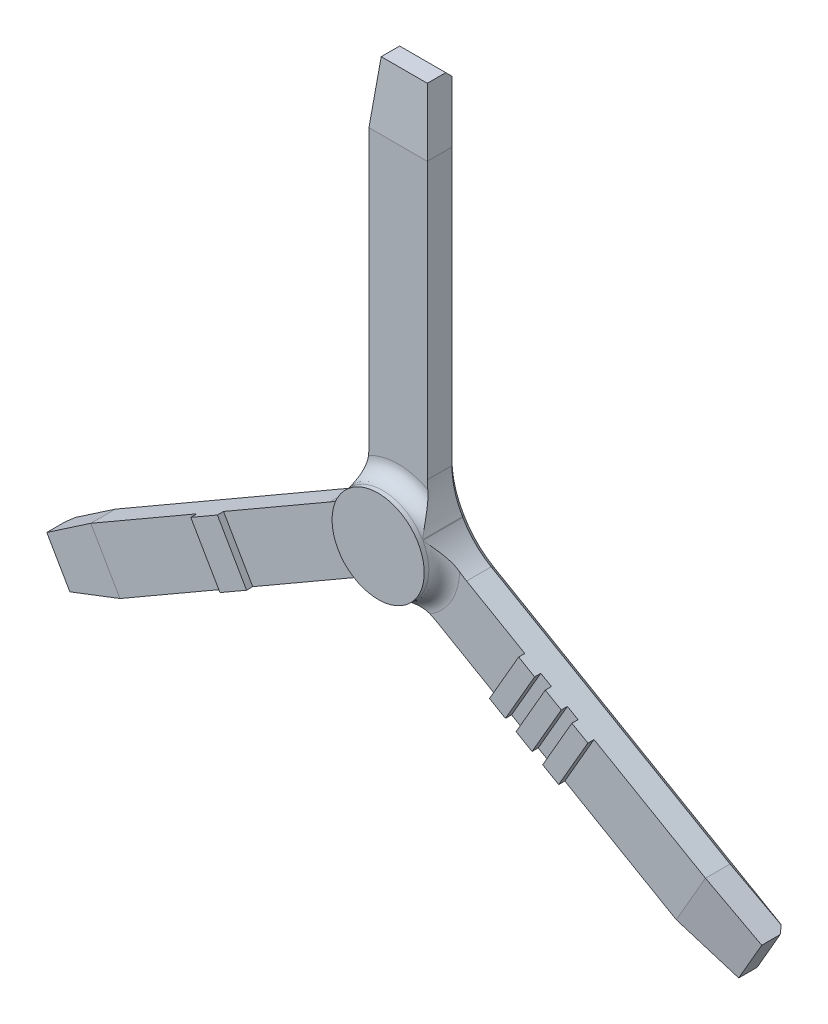
SolidWorks part; units mm, degrees
ref_plane "Front Plane" through (0, 0, 0) normal (0, 0, 1) x (1, 0, 0)
ref_plane "Top Plane" through (0, 0, 0) normal (0, 1, 0) x (1, 0, 0)
ref_plane "Right Plane" through (0, 0, 0) normal (1, 0, 0) x (0, 0, -1)
sketch "Sketch1" plane through (0, 0, 0) normal (0, 0, 1) x (1, 0, 0)
  line L0 (-1.9, 24) -> (1.9, 24) construction
  line L1 (0, 0) -> (0, 24) construction
  line L2 (-1.9, 24) -> (-1.9, 26)
  line L3 (-1.9, 26) -> (1.9, 26)
  line L4 (1.9, 26) -> (1.9, 24)
  line L5 (23.4667, -11.3546) -> (21.5667, -14.6454)
  line L6 (21.5667, -14.6454) -> (19.8346, -13.6454)
  line L7 (21.7346, -10.3546) -> (23.4667, -11.3546)
  line L8 (-21.5667, -14.6454) -> (-23.4667, -11.3546)
  line L9 (-23.4667, -11.3546) -> (-21.7346, -10.3546)
  line L10 (-19.8346, -13.6454) -> (-21.5667, -14.6454)
  line L11 (0, 0) -> (1.9, 24) construction
  line L12 (0, 0) -> (19.8346, -13.6454) construction
  line L13 (-1.9, 24) -> (-1.9, 1.097)
  line L14 (-1.9, 1.097) -> (-21.7346, -10.3546)
  line L15 (-19.8346, -13.6454) -> (0, -2.1939)
  line L16 (0, -2.1939) -> (19.8346, -13.6454)
  line L17 (21.7346, -10.3546) -> (1.9, 1.097)
  line L18 (1.9, 1.097) -> (1.9, 24)
  circle A0 centre (0, 0) radius 24 construction
  dimension "D1" = 48
  dimension "D2" = 3.8
  dimension "D3" = 2
  dimension "D4" = 120
  dimension "D5" = 24.0751
  dimension "D6" = 3
extrude "Boss-Extrude1" add sketch "Sketch1" along normal blind 2 contours L18 A0 L13 L14 L15 L16 L17 region at (0, 0, 0)
chamfer "Chamfer1" distance 4 distance2 0.4 3 edges at (22.5167, -13, 2) (-22.5167, -13, 2) (0, 26, 2) first distance on face at (0, 0, 2)
chamfer "Chamfer2" distance 0.4 distance2 4 3 edges at (23.4667, -11.3546, 0.8) (-1.9, 26, 0.8) (-21.5667, -14.6454, 0.8) first distance on face at (22.5167, -13, 0.8) first distance on face at (0, 26, 0.8) first distance on face at (-22.5167, -13, 0.8)
chamfer "Chamfer3" distance 4 distance2 0.4 3 edges at (1.9, 26, 0.8) (21.5667, -14.6454, 0.8) (-23.4667, -11.3546, 0.8) first distance on face at (1.9, 15.2388, 1.12) first distance on face at (12.2472, -9.2648, 1.12) first distance on face at (-14.1472, -5.9739, 1.12)
sketch "Sketch2" plane through (0, 0, 0) normal (0, 0, -1) x (-1, 0, 0)
  circle A0 centre (0, 0) radius 3
  dimension "D1" = 6
extrude "Boss-Extrude2" add sketch "Sketch2" against normal blind 3.3
fillet "Fillet1" radius 5 6 edges at (1.9, 2.3216, 1) (2.9606, 0.4846, 1) (1.0606, -2.8063, 1) (-1.0606, -2.8063, 1) (-2.9606, 0.4846, 1) (-1.9, 2.3216, 1)
fillet "Fillet2" radius 1 3 edges at (0, 3, 2) (2.5981, -1.5, 2) (-2.5981, -1.5, 2)
chamfer "Chamfer4" distance 0.4 angle 45 18 edges at (22.5167, -13, 0) (-22.5167, -13, 0) (0, 26, 0) (12.2293, -4.8667, 0) (3.4082, 0.4282, 0) (2.5981, 1.5, 0) (2.0749, 2.7374, 0) (1.9, 13.0242, 0) (-12.2293, -4.8667, 0) (-3.4082, 0.4282, 0) (-2.5981, 1.5, 0) (-2.0749, 2.7374, 0) (-1.9, 13.0242, 0) (10.3293, -8.1576, 0) (1.3332, -3.1657, 0) (0, -3, 0) (-1.3332, -3.1657, 0) (-10.3293, -8.1576, 0)
sketch "Sketch3" plane through (0, 0, 2) normal (0, 0, 1) x (1, 0, 0)
  line L0 (-12.2293, -4.8667) -> (-10.3293, -8.1576) construction
  line L1 (-4.4561, -0.3788) -> (-20.0026, -9.3546) construction
  line L2 (-2.5561, -3.6697) -> (-18.1026, -12.6454) construction
  line L3 (-13.0953, -5.3667) -> (-11.1953, -8.6576)
  line L4 (2.5561, -3.6697) -> (18.1026, -12.6454) construction
  line L5 (10.3293, -8.1576) -> (12.2293, -4.8667) construction
  line L6 (20.0026, -9.3546) -> (4.4561, -0.3788) construction
  line L7 (-13.0953, -5.3667) -> (-11.3633, -4.3667)
  line L8 (-11.1953, -8.6576) -> (-9.4633, -7.6576)
  line L9 (-11.3633, -4.3667) -> (-9.4633, -7.6576)
  line L10 (-13.0953, -5.3667) -> (-9.4633, -7.6576) construction
  line L11 (-11.1953, -8.6576) -> (-11.3633, -4.3667) construction
  line L12 (11.7097, -4.5667) -> (9.8097, -7.8576)
  line L13 (11.7097, -4.5667) -> (12.7489, -5.1667)
  line L14 (9.8097, -7.8576) -> (10.8489, -8.4576)
  line L15 (12.7489, -5.1667) -> (10.8489, -8.4576)
  line L16 (11.7097, -4.5667) -> (10.8489, -8.4576) construction
  line L17 (9.8097, -7.8576) -> (12.7489, -5.1667) construction
  line L18 (8.0776, -6.8576) -> (9.1169, -7.4576)
  line L19 (11.0169, -4.1667) -> (9.1169, -7.4576)
  line L20 (9.9776, -3.5667) -> (8.0776, -6.8576)
  line L21 (9.9776, -3.5667) -> (11.0169, -4.1667)
  line L22 (6.3456, -5.8576) -> (7.3848, -6.4576)
  line L23 (9.2848, -3.1667) -> (7.3848, -6.4576)
  line L24 (8.2456, -2.5667) -> (6.3456, -5.8576)
  line L25 (8.2456, -2.5667) -> (9.2848, -3.1667)
  point P13 (-11.2793, -6.5121)
  point P14 (11.2793, -6.5121)
  dimension "D1" = 2
  dimension "D2" = 1.2
  dimension "D3" = 3
extrude "Boss-Extrude3" add sketch "Sketch3" along normal blind 0.4
